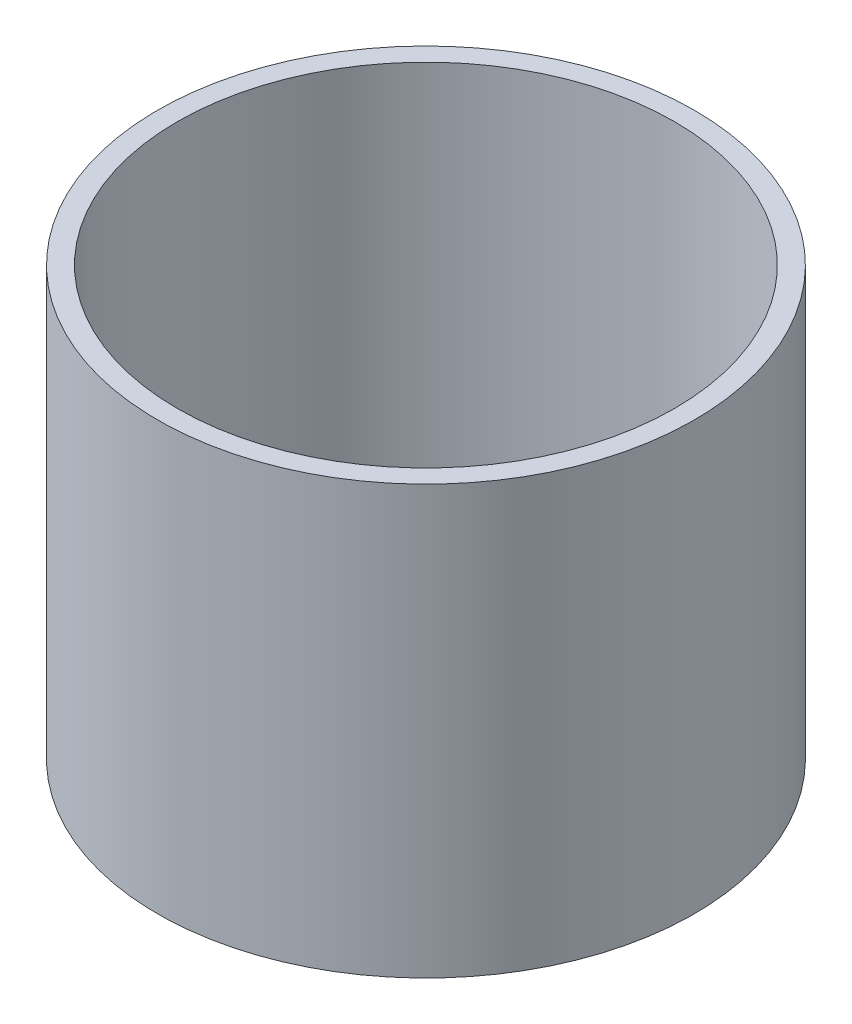
SolidWorks part; units mm, degrees
ref_plane "Front Plane" through (0, 0, 0) normal (0, 0, 1) x (1, 0, 0)
ref_plane "Top Plane" through (0, 0, 0) normal (0, 1, 0) x (1, 0, 0)
ref_plane "Right Plane" through (0, 0, 0) normal (1, 0, 0) x (0, 0, -1)
sketch "Sketch1" plane through (0, 0, 0) normal (0, 1, 0) x (1, 0, 0)
  circle A0 centre (0, 0) radius 13.55
  dimension "D1" = 27.1
extrude "Boss-Extrude1" add sketch "Sketch1" along normal blind 21.6
shell "Shell4" thickness 1 removed face at (0, 21.6, 13.55)
hole_wizard "M2x0.4 Tapped Hole1" positions "Sketch2" profile "Sketch3" tap size "M2x0.4" standard "ANSI Metric" end condition through all
sketch "Sketch2" plane through (0, 21.6, 0) normal (0, 1, 0) x (1, 0, 0)
  line L0 (13.55, 0) -> (-13.55, 0) construction
  line L2 (0, -13.55) -> (0, 13.55) construction
  circle A0 centre (0, 0) radius 13.55 construction
  point P0 (0, 6)
  point P20 (6, 0)
  point P21 (0, -6)
  point P22 (-6, 0)
  dimension "D1" = 12
  dimension "D2" = 4
sketch "Sketch3" plane through (0, 21.6, -6) normal (1, 0, 0) x (0, 0, 1)
  line L0 (0, 0) -> (0, 21.6)
  line L1 (0, 21.6) -> (0.8, 21.6)
  line L2 (0.8, 21.6) -> (0.8, 0)
  line L5 (0.8, 0) -> (0, 0)
  line L11 (0, -6.35) -> (0, 107.95) construction
  dimension "Thru Tap Drill Dia." = 1.6
  dimension "Thru Tap Drill Depth" = 21.6
cosmetic thread "Hole Thread6"
cosmetic thread "Hole Thread7"
cosmetic thread "Hole Thread8"
cosmetic thread "Hole Thread9"
sketch "Sketch4" plane through (0, 0, 0) normal (0, -1, 0) x (1, 0, 0)
  circle A0 centre (0, 0) radius 4.35
  dimension "D1" = 8.7
extrude "Boss-Extrude2" add sketch "Sketch4" along normal blind 1.5
